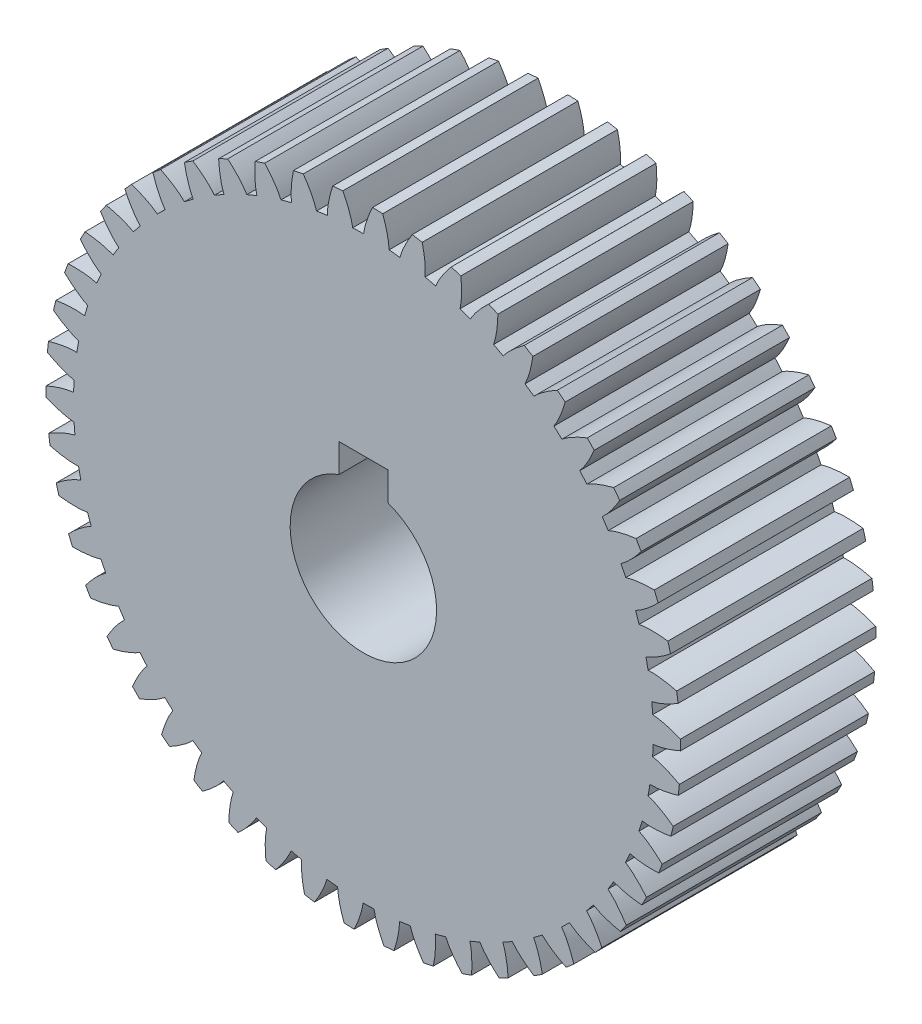
SolidWorks part; units mm, degrees
ref_plane "Front Plane" through (0, 0, 0) normal (0, 0, 1) x (1, 0, 0)
ref_plane "Top Plane" through (0, 0, 0) normal (0, 1, 0) x (1, 0, 0)
ref_plane "Right Plane" through (0, 0, 0) normal (1, 0, 0) x (0, 0, -1)
sketch "Involute Geometry" plane through (0, 0, 0) normal (0, 0, 1) x (1, 0, 0)
  line L0 (0, 23.4923) -> (0, 0) construction
  line L1 (0, 0) -> (1.1665, 25.9738) construction
  line L2 (2.1059, 23.3977) -> (0, 0) construction
  line L3 (0.3366, 24.9977) -> (0, 0) construction
  line L4 (0, 0) -> (1.9056, 24.9273) construction
  circle A1 centre (0, 0) radius 23.4923 construction
  circle A2 centre (0, 0) radius 25 construction
  circle A3 centre (0, 0) radius 26 construction
  circle A4 centre (0, 0) radius 23.75 construction
  arc A5 (0.7536, 25.9891) -> (1.5791, 25.952) centre (0, 0) cw
  arc A6 (0.3366, 24.9977) -> (1.9056, 24.9273) centre (0, 0) cw construction
  spline S0 degree 4 poles (0, 23.4923) (0, 23.5114) (0.0013, 23.5648) (0.0089, 23.6656) (0.0287, 23.8296) (0.081, 24.1325) (0.1926, 24.5862) (0.3554, 25.0766) (0.5626, 25.5852) (0.7677, 26.0245) (0.9438, 26.37) (1.171, 26.7822) (1.4642, 27.2682) (1.8332, 27.8211) (2.2875, 28.4323) (2.7797, 29.0321) (3.2982, 29.6089) (3.8411, 30.1634) (4.4053, 30.6951) (4.9175, 31.1416) (5.3665, 31.5096) (5.7503, 31.8087) (6.0572, 32.04) (6.3766, 32.2711) (6.6846, 32.4876) (7.0225, 32.7147) (7.3185, 32.909) (7.7622, 33.1868) (8.0307, 33.348) (8.4647, 33.6019) (8.6612, 33.7084) (8.8384, 33.8077) (8.891, 33.8352) (8.9294, 33.8561) (8.9501, 33.8675) knots 0 0 0 0 0 0.005377 0.015084 0.028532 0.04661 0.092111 0.146842 0.174209 0.201575 0.228941 0.256307 0.307035 0.361767 0.4165 0.471232 0.525964 0.580697 0.635429 0.690161 0.717528 0.744894 0.77226 0.799626 0.826992 0.854358 0.881725 0.909091 0.954545 0.977273 0.988636 0.994318 1 1 1 1 1 construction
  spline S1 degree 4 poles (0, 23.4923) (0, 23.5114) (0.0013, 23.5648) (0.0089, 23.6656) (0.0287, 23.8296) (0.081, 24.1325) (0.1926, 24.5862) (0.3554, 25.0766) (0.5626, 25.5852) (0.7677, 26.0245) (0.9438, 26.37) (1.171, 26.7822) (1.4642, 27.2682) (1.8332, 27.8211) (2.2875, 28.4323) (2.7797, 29.0321) (3.2982, 29.6089) (3.8411, 30.1634) (4.4053, 30.6951) (4.9175, 31.1416) (5.3665, 31.5096) (5.7503, 31.8087) (6.0572, 32.04) (6.3766, 32.2711) (6.6846, 32.4876) (7.0225, 32.7147) (7.3185, 32.909) (7.6041, 33.0878) (7.7558, 33.1811) (7.8311, 33.2268) knots 0 0 0 0 0 0.005377 0.015084 0.028532 0.04661 0.092111 0.146842 0.174209 0.201575 0.228941 0.256307 0.307035 0.361767 0.4165 0.471232 0.525964 0.580697 0.635429 0.690161 0.717528 0.744894 0.77226 0.799626 0.826992 0.854358 0.881725 0.909091 0.909091 0.909091 0.909091 0.909091
  spline S3 degree 4 poles (2.1059, 23.3977) (2.1076, 23.4167) (2.1111, 23.47) (2.1125, 23.5712) (2.1075, 23.7362) (2.0826, 24.0426) (2.0121, 24.5045) (1.8939, 25.0075) (1.7332, 25.5326) (1.5683, 25.9886) (1.4238, 26.3485) (1.2345, 26.7793) (0.9861, 27.2897) (0.6681, 27.8734) (0.2705, 28.5229) (-0.166, 29.1644) (-0.6307, 29.7854) (-1.1217, 30.3863) (-1.636, 30.9664) (-2.1061, 31.457) (-2.5203, 31.8638) (-2.8757, 32.1961) (-3.1606, 32.454) (-3.4581, 32.7128) (-3.7454, 32.9561) (-4.0616, 33.2125) (-4.339, 33.4325) (-4.756, 33.749) (-5.009, 33.9336) (-5.4185, 34.2255) (-5.6047, 34.3491) (-5.7723, 34.4639) (-5.8222, 34.4959) (-5.8585, 34.5202) (-5.8781, 34.5334) knots 0 0 0 0 0 0.005377 0.015084 0.028532 0.04661 0.092111 0.146842 0.174209 0.201575 0.228941 0.256307 0.307035 0.361767 0.4165 0.471232 0.525964 0.580697 0.635429 0.690161 0.717528 0.744894 0.77226 0.799626 0.826992 0.854358 0.881725 0.909091 0.954545 0.977273 0.988636 0.994318 1 1 1 1 1 construction
  spline S4 degree 4 poles (2.1059, 23.3977) (2.1076, 23.4167) (2.1111, 23.47) (2.1125, 23.5712) (2.1075, 23.7362) (2.0826, 24.0426) (2.0121, 24.5045) (1.8939, 25.0075) (1.7332, 25.5326) (1.5683, 25.9886) (1.4238, 26.3485) (1.2345, 26.7793) (0.9861, 27.2897) (0.6681, 27.8734) (0.2705, 28.5229) (-0.166, 29.1644) (-0.6307, 29.7854) (-1.1217, 30.3863) (-1.636, 30.9664) (-2.1061, 31.457) (-2.5203, 31.8638) (-2.8757, 32.1961) (-3.1606, 32.454) (-3.4581, 32.7128) (-3.7454, 32.9561) (-4.0616, 33.2125) (-4.339, 33.4325) (-4.6074, 33.6362) (-4.7502, 33.7427) (-4.8211, 33.795) knots 0 0 0 0 0 0.005377 0.015084 0.028532 0.04661 0.092111 0.146842 0.174209 0.201575 0.228941 0.256307 0.307035 0.361767 0.4165 0.471232 0.525964 0.580697 0.635429 0.690161 0.717528 0.744894 0.77226 0.799626 0.826992 0.854358 0.881725 0.909091 0.909091 0.909091 0.909091 0.909091
  dimension "D5" = 3.6
sketch "Sketch2" plane through (0, 0, 0) normal (0, 0, 1) x (1, 0, 0)
  circle A0 centre (0, 0) radius 23.75 construction
  circle A1 centre (0, 0) radius 23.75
extrude "Boss-Extrude1" add sketch "Sketch2" along normal mid plane 16
sketch "Sketch3" plane through (0, 0, 0) normal (0, 0, 1) x (1, 0, 0)
  arc A3 (0.0199, 23.75) -> (2.1092, 23.6562) centre (0, 0) cw
  arc A4 (1.5791, 25.952) -> (0.7536, 25.9891) centre (0, 0) ccw construction
  arc A5 (1.5791, 25.952) -> (0.7536, 25.9891) centre (0, 0) ccw
  circle A7 centre (0, 0) radius 23.75 construction
  spline S0 degree 4 poles (999.8204, 40.2462) (20.7121, 20.125) (0.4503, 21.1025) (-0.1347, 22.474) (0.0287, 23.8296) (0.081, 24.1325) (0.1926, 24.5862) (0.3554, 25.0766) (0.5626, 25.5852) (0.7677, 26.0245) (0.9438, 26.37) (1.171, 26.7822) (1.4642, 27.2682) (1.8332, 27.8211) (2.2875, 28.4323) (2.7797, 29.0321) (3.2982, 29.6089) (3.8411, 30.1634) (4.4053, 30.6951) (4.9175, 31.1416) (5.3665, 31.5096) (5.7503, 31.8087) (6.0572, 32.04) (6.3766, 32.2711) (6.6846, 32.4876) (7.0225, 32.7147) (8.3806, 33.6059) (11.7895, 35.5553) (-19.6779, 16.1915) (862.8738, 551.731) knots -0.338747 -0.338747 -0.338747 -0.338747 -0.338747 0.005377 0.015084 0.028532 0.04661 0.092111 0.146842 0.174209 0.201575 0.228941 0.256307 0.307035 0.361767 0.4165 0.471232 0.525964 0.580697 0.635429 0.690161 0.717528 0.744894 0.77226 0.799626 0.826992 0.854358 0.881725 1.301773 1.301773 1.301773 1.301773 1.301773 only from (0, 23.4923) to (7.5082, 22.3415) construction
  spline S1 degree 4 poles (0.0199, 23.75) (0.0244, 23.7861) (0.0384, 23.8856) (0.0837, 24.1434) (0.1926, 24.5862) (0.3677, 25.1136) (0.5556, 25.5675) (0.6944, 25.8667) (0.7536, 25.9891) knots 0.018251 0.018251 0.018251 0.018251 0.018251 0.028532 0.04661 0.092111 0.146842 0.185208 0.185208 0.185208 0.185208 0.185208
  spline S3 degree 4 poles (-992.1874, 129.7099) (-18.8247, 21.9006) (1.4432, 21.0579) (2.1488, 22.3715) (2.1075, 23.7362) (2.0826, 24.0426) (2.0121, 24.5045) (1.8939, 25.0075) (1.7332, 25.5326) (1.5683, 25.9886) (1.4238, 26.3485) (1.2345, 26.7793) (0.9861, 27.2897) (0.6681, 27.8734) (0.2705, 28.5229) (-0.166, 29.1644) (-0.6307, 29.7854) (-1.1217, 30.3863) (-1.636, 30.9664) (-2.1061, 31.457) (-2.5203, 31.8638) (-2.8757, 32.1961) (-3.1606, 32.454) (-3.4581, 32.7128) (-3.7454, 32.9561) (-4.0616, 33.2125) (-5.3344, 34.2219) (-8.5548, 36.469) (21.0501, 14.3623) (-809.9417, 626.8594) knots -0.338747 -0.338747 -0.338747 -0.338747 -0.338747 0.005377 0.015084 0.028532 0.04661 0.092111 0.146842 0.174209 0.201575 0.228941 0.256307 0.307035 0.361767 0.4165 0.471232 0.525964 0.580697 0.635429 0.690161 0.717528 0.744894 0.77226 0.799626 0.826992 0.854358 0.881725 1.301773 1.301773 1.301773 1.301773 1.301773 only from (2.1059, 23.3977) to (-4.8211, 33.795) construction
  spline S4 degree 4 poles (2.1092, 23.6562) (2.1079, 23.6925) (2.1029, 23.7929) (2.0809, 24.0537) (2.0121, 24.5045) (1.885, 25.0455) (1.7385, 25.5144) (1.6271, 25.8248) (1.5791, 25.952) knots 0.018251 0.018251 0.018251 0.018251 0.018251 0.028532 0.04661 0.092111 0.146842 0.185208 0.185208 0.185208 0.185208 0.185208
extrude "Boss-Extrude2" add sketch "Sketch3" along normal through all and the other way through all
fillet "Fillet2" [suppressed] radius 0.381
pattern_circular "CirPattern1" count 50 over 360 about axis through (0, 0, 8) along (0, 0, -1) of "Boss-Extrude2", "Fillet2"
ref_axis "Axis1" through (0, 0, 8) along (0, 0, -1)
sketch "Sketch4" plane through (0, 0, -8) normal (0, 0, -1) x (-1, 0, 0)
  circle A1 centre (0, 0) radius 6
  dimension "D1" = 12
extrude "Cut-Extrude1" cut sketch "Sketch4" against normal through all
sketch "Sketch5" plane through (0, 0, -8) normal (0, 0, -1) x (-1, 0, 0)
  line L1 (-2, 8) -> (2, 8)
  line L2 (-2, 8) -> (-2, 5.6569)
  line L3 (-2, 5.6569) -> (2, 5.6569)
  line L4 (2, 8) -> (2, 5.6569)
  line L5 (-2, 8) -> (2, 5.6569) construction
  line L6 (-2, 5.6569) -> (2, 8) construction
  circle A0 centre (0, 0) radius 6 construction
  point P0 (0, 6.8284)
  dimension "D1" = 4
  dimension "D2" = 2
extrude "Cut-Extrude2" cut sketch "Sketch5" against normal through all
equation "\"N\"= 50'Number of Teeth"
equation "\"m\"= 1mm'Diametral Pitch"
equation "\"phi\"= 20deg'Pressure Angle"
equation "\"a\"= \"m\"'Addendum"
equation "\"b\"= 1.25 * \"m\"'Dedendum"
equation "\"Dp\"= \"N\" * \"m\"'Pitch diameter"
equation "\"Db\"= \"Dp\" * cos ( \"phi\" )'Base diameter"
equation "\"D1@Involute Geometry\" = \"Db\""
equation "\"D2@Involute Geometry\" = \"Dp\""
equation "\"D3@Involute Geometry\" = \"Dp\" + 2 * \"a\""
equation "\"D4@Involute Geometry\" = \"Dp\" - 2 * \"b\""
equation "\"D1@CirPattern1\"=\"N\""
equation "\"D5@Involute Geometry\"=180/\"N\""
equation "\"D1@Boss-Extrude1\"=16*\"m\""
equation "\"alpha\"= sqr ( \"Dp\" ^ 2 - \"Db\" ^ 2 ) / \"Db\" * 180 / pi - \"phi\""
equation "\"beta\"= ( ( 360deg / \"N\" ) / 4 - \"alpha\" )"
